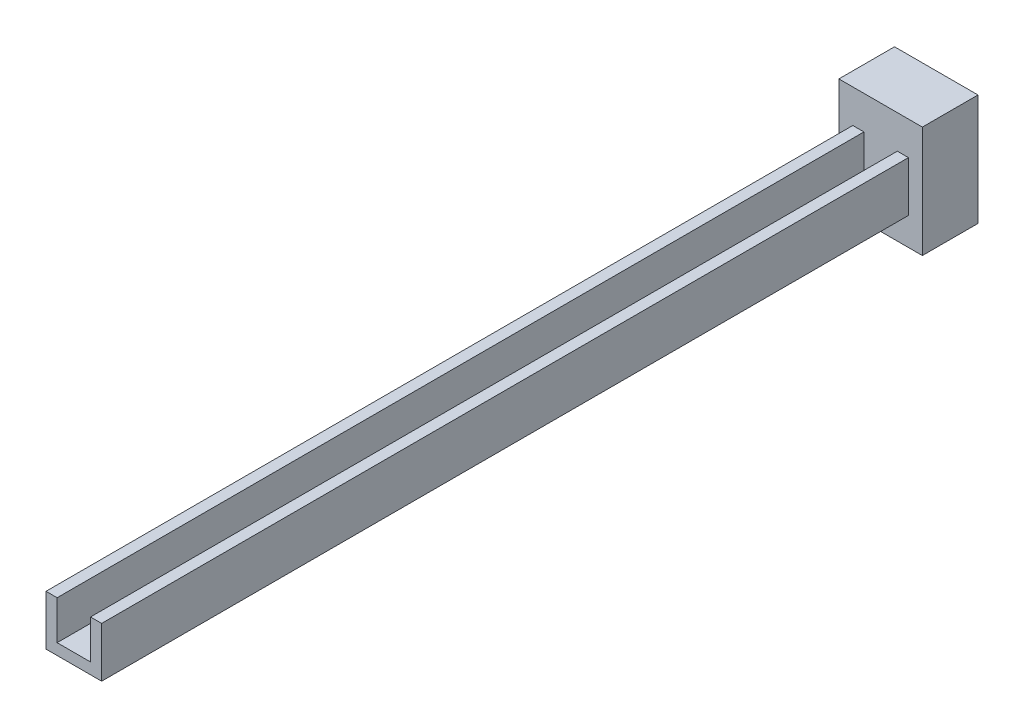
SolidWorks part; units mm, degrees
ref_plane "正面" through (0, 0, 0) normal (0, 0, 1) x (1, 0, 0)
ref_plane "平面" through (0, 0, 0) normal (0, 1, 0) x (1, 0, 0)
ref_plane "右側面" through (0, 0, 0) normal (1, 0, 0) x (0, 0, -1)
sketch "ｽｹｯﾁ1" plane through (0, 0, 0) normal (0, 0, 1) x (1, 0, 0)
  line L0 (-5, 9) -> (-5, 0)
  line L1 (-5, 0) -> (5, 0)
  line L2 (5, 0) -> (5, 9)
  line L3 (5, 9) -> (3, 9)
  line L4 (3, 9) -> (3, 2)
  line L5 (3, 2) -> (-3, 2)
  line L6 (-3, 2) -> (-3, 9)
  line L7 (-3, 9) -> (-5, 9)
  dimension "D1" = 9
  dimension "D2" = 9
  dimension "D3" = 10
  dimension "D4" = 5
  dimension "D5" = 2
  dimension "D6" = 2
  dimension "D7" = 2
extrude "ﾎﾞｽ - 押し出し1" add sketch "ｽｹｯﾁ1" along normal blind 245
sketch "ｽｹｯﾁ2" plane through (0, 0, 0) normal (0, -1, 0) x (1, 0, 0)
  line L0 (-5, 245) -> (5, 245) construction
  circle A0 centre (0, 225) radius 2.5
  circle A1 centre (0, 217) radius 2.5
  circle A2 centre (0, 122.5) radius 2.5
  circle A3 centre (0, 209) radius 2.5
  circle A4 centre (0, 193) radius 2.5
  circle A5 centre (0, 161) radius 2.5
  dimension "D1" = 20
  dimension "D3" = 5
  dimension "D4" = 5
  dimension "D5" = 5
  dimension "D6" = 122.5
  dimension "D7" = 5
  dimension "D8" = 8
  dimension "D9" = 5
  dimension "D10" = 16
  dimension "D11" = 5
  dimension "D12" = 32
  dimension "D2" = 28
extrude "ｶｯﾄ - 押し出し1" cut sketch "ｽｹｯﾁ2" against normal through all
ref_plane "平面1" through (0, 0, 122.5) normal (0, 0, 1) x (1, 0, 0)
mirror "ﾐﾗｰ1" about plane through (0, 0, 122.5) normal (0, 0, 1) of "ｶｯﾄ - 押し出し1"
sketch "ｽｹｯﾁ3" plane through (0, 0, 0) normal (0, -1, 0) x (1, 0, 0)
  line L0 (-5, 0) -> (-5, 100)
  line L1 (-5, 245) -> (-5, 0) construction
  line L2 (-5, 100) -> (5, 100)
  line L3 (5, 245) -> (5, 0) construction
  line L4 (5, 100) -> (5, 0)
  line L5 (5, 0) -> (-5, 0)
  dimension "D1" = 100
extrude "ｶｯﾄ - 押し出し2" cut sketch "ｽｹｯﾁ3" against normal through all both
sketch "ｽｹｯﾁ5" plane through (0, 0, 100) normal (0, 0, -1) x (-1, 0, 0)
  line L0 (-7.5, 15) -> (-7.5, -5)
  line L1 (-7.5, -5) -> (7.5, -5)
  line L2 (7.5, -5) -> (7.5, 15)
  line L3 (7.5, 15) -> (-7.5, 15)
  dimension "D1" = 15
  dimension "D2" = 7.5
  dimension "D3" = 20
  dimension "D4" = 15
extrude "ﾎﾞｽ - 押し出し3" add sketch "ｽｹｯﾁ5" along normal blind 10
equation "\"D2@ｽｹｯﾁ5\"=\"D1@ｽｹｯﾁ5\"/2"
